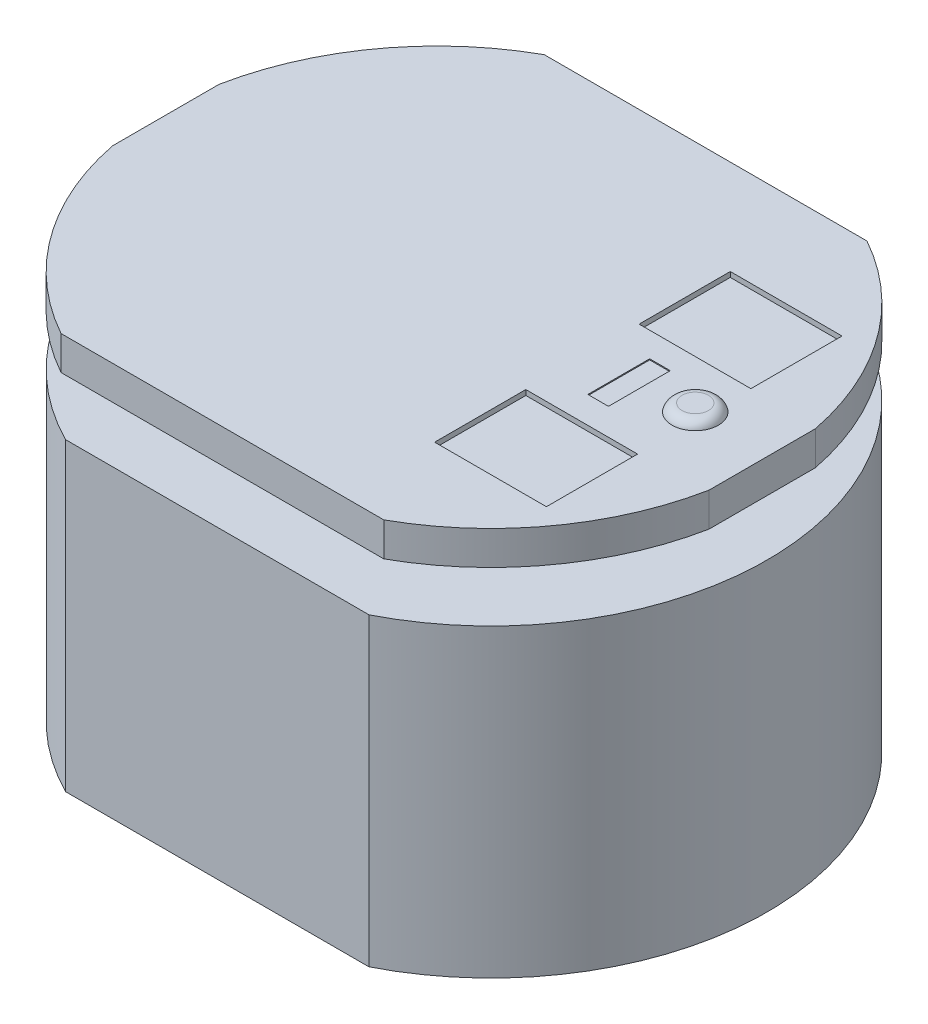
SolidWorks part; units mm, degrees
ref_plane "Plano frontal" through (0, 0, 0) normal (0, 0, 1) x (1, 0, 0)
ref_plane "Plano superior" through (0, 0, 0) normal (0, 1, 0) x (1, 0, 0)
ref_plane "Plano direito" through (0, 0, 0) normal (1, 0, 0) x (0, 0, -1)
sketch "Esboço1" plane through (0, 0, 0) normal (0, 1, 0) x (1, 0, 0)
  line L1 (294.5, -239.5) -> (-294.5, -239.5)
  line L2 (294.5, -239.5) -> (294.5, 239.5)
  line L3 (294.5, 239.5) -> (-294.5, 239.5)
  line L4 (-294.5, -239.5) -> (-294.5, 239.5)
  line L5 (294.5, -239.5) -> (-294.5, 239.5) construction
  line L6 (294.5, 239.5) -> (-294.5, -239.5) construction
  point P0 (0, 0)
  dimension "D1" = 589
  dimension "D2" = 479
extrude "Ressalto-extrusão1" add sketch "Esboço1" along normal blind 296
sketch "Esboço2" plane through (0, 296, 0) normal (0, 1, 0) x (1, 0, 0)
  line L1 (-110, 90) -> (110, 90)
  line L2 (-110, 90) -> (-110, -90)
  line L3 (-110, -90) -> (110, -90)
  line L4 (110, 90) -> (110, -90)
  line L5 (-110, 90) -> (110, -90) construction
  line L6 (-110, -90) -> (110, 90) construction
  point P0 (0, 0)
  dimension "D1" = 220
  dimension "D2" = 180
extrude "Ressalto-extrusão2" add sketch "Esboço2" along normal blind 49.2
sketch "Esboço3" plane through (0, 345.2, 0) normal (0, 1, 0) x (1, 0, 0)
  line L1 (-289.5, 234.5) -> (289.5, 234.5)
  line L2 (-289.5, 234.5) -> (-289.5, -234.5)
  line L3 (-289.5, -234.5) -> (289.5, -234.5)
  line L4 (289.5, 234.5) -> (289.5, -234.5)
  line L5 (-289.5, 234.5) -> (289.5, -234.5) construction
  line L6 (-289.5, -234.5) -> (289.5, 234.5) construction
  point P0 (0, 0)
  dimension "D1" = 579
  dimension "D2" = 469
extrude "Ressalto-extrusão3" add sketch "Esboço3" along normal blind 32.8
sketch "Esboço4" plane through (0, 378, 0) normal (0, 1, 0) x (1, 0, 0)
  line L0 (0, 239.5) -> (0, -239.5) construction
  line L1 (294.5, 239.5) -> (-294.5, 239.5) construction
  line L3 (147.25, 239.5) -> (-147.25, 239.5) construction
  line L4 (-294.5, -239.5) -> (294.5, -239.5) construction
  line L5 (-147.25, -239.5) -> (147.25, -239.5) construction
  line L6 (-294.5, 239.5) -> (-294.5, -239.5) construction
  line L8 (-147.25, 239.5) -> (-294.5, 239.5)
  line L9 (-294.5, 239.5) -> (-294.5, -239.5)
  line L10 (-294.5, -239.5) -> (-147.25, -239.5)
  line L11 (147.25, -239.5) -> (294.5, -239.5)
  line L12 (294.5, -239.5) -> (294.5, 239.5)
  line L13 (294.5, 239.5) -> (147.25, 239.5)
  arc A0 (-147.25, 239.5) -> (-147.25, -239.5) centre (-26.1034, 0) ccw
  arc A1 (147.25, 239.5) -> (147.25, -239.5) centre (26.1034, 0) cw
  arc A2 (147.25, 239.5) -> (147.25, -239.5) centre (26.1034, 0) cw
  point P14 (-294.5, 0)
  line M3 (289.5, -234.5) -> (289.5, 234.5)
  line M4 (289.5, 234.5) -> (-289.5, 234.5)
  line M5 (-289.5, 234.5) -> (-289.5, -234.5)
  line M6 (-289.5, -234.5) -> (289.5, -234.5)
  dimension "D1" = 147.25
extrude "Corte-extrusão1" cut sketch "Esboço4" against normal up to surface (378 mm away) contours A0 M5 M6 | A0 M4 M5 | A1 M4 M3 | A1 M3 M6 | L13 A1 L12 M4 M3 | L12 A1 L11 M3 M6 | A0 L9 L10 M6 M5 | A0 L8 L9 M5 M4 region at (-152.1145, 378, -237.2951) region at (-251.6024, 378, -184.7117) region at (-293.5269, 378, 25.9306) region at (251.6024, 378, -184.7117) region at (152.1145, 378, -237.2951) region at (-251.6024, 378, 184.7117) region at (291.6885, 378, 119.75) region at (251.6024, 378, 184.7117) up to face at (0, 0, 0)
sketch "Esboço5" plane through (0, 378, 0) normal (0, 1, 0) x (1, 0, 0)
  line L0 (-156.6656, -234.5) -> (156.6656, -234.5) construction
  line L1 (116, -144.5) -> (224.5, -144.5)
  line L2 (116, -144.5) -> (116, -56)
  line L3 (116, -56) -> (224.5, -56)
  line L4 (224.5, -144.5) -> (224.5, -56)
  line L5 (116, -144.5) -> (224.5, -56) construction
  line L6 (116, -56) -> (224.5, -144.5) construction
  line L7 (116, 54) -> (224.5, 54)
  line L8 (116, 54) -> (116, 142.5)
  line L9 (116, 142.5) -> (224.5, 142.5)
  line L10 (224.5, 54) -> (224.5, 142.5)
  line L11 (116, 54) -> (224.5, 142.5) construction
  line L12 (116, 142.5) -> (224.5, 54) construction
  arc A0 (147.25, -239.5) -> (147.25, 239.5) centre (26.1034, 0) ccw construction
  point P0 (170.25, -100.25)
  point P5 (170.25, 98.25)
  point P10 (0, 0)
  point P16 (294.5, 0)
  dimension "D1" = 88.5
  dimension "D2" = 108.5
  dimension "D3" = 90
  dimension "D4" = 110
  dimension "D5" = 70
extrude "Corte-extrusão2" cut sketch "Esboço5" against normal blind 5
sketch "Esboço6" plane through (0, 378, 0) normal (0, 1, 0) x (1, 0, 0)
  line L1 (224.5, -144.5) -> (224.5, -56) construction
  circle A0 centre (224.5, 0) radius 10
  point P2 (0, 0)
  point P7 (224.5, -100.25)
  dimension "D1" = 20
extrude "Ressalto-extrusão4" add sketch "Esboço6" along normal blind 7.5
sketch "Esboço7" plane through (0, 385.5, 0) normal (0, 1, 0) x (1, 0, 0)
  circle A0 centre (224.5, 0) radius 22.5
  dimension "D1" = 45
extrude "Ressalto-extrusão5" add sketch "Esboço7" along normal blind 7.5
fillet "Filete1" radius 10 1 edges at (224.5, 393, 22.5)
sketch "Esboço8" plane through (0, 378, 0) normal (0, 1, 0) x (1, 0, 0)
  line L1 (170.25, 30) -> (150.25, 30)
  line L2 (170.25, 30) -> (170.25, -30)
  line L3 (170.25, -30) -> (150.25, -30)
  line L4 (150.25, 30) -> (150.25, -30)
  line L5 (170.25, 30) -> (150.25, -30) construction
  line L6 (170.25, -30) -> (150.25, 30) construction
  line L7 (116, 54) -> (224.5, 54) construction
  line L8 (116, 54) -> (224.5, 54) construction
  point P0 (160.25, 0)
  point P9 (170.25, 54)
  dimension "D1" = 20
  dimension "D2" = 60
  dimension "D3" = 10
  dimension "D4" = 24
extrude "Corte-extrusão3" cut sketch "Esboço8" against normal blind 1
